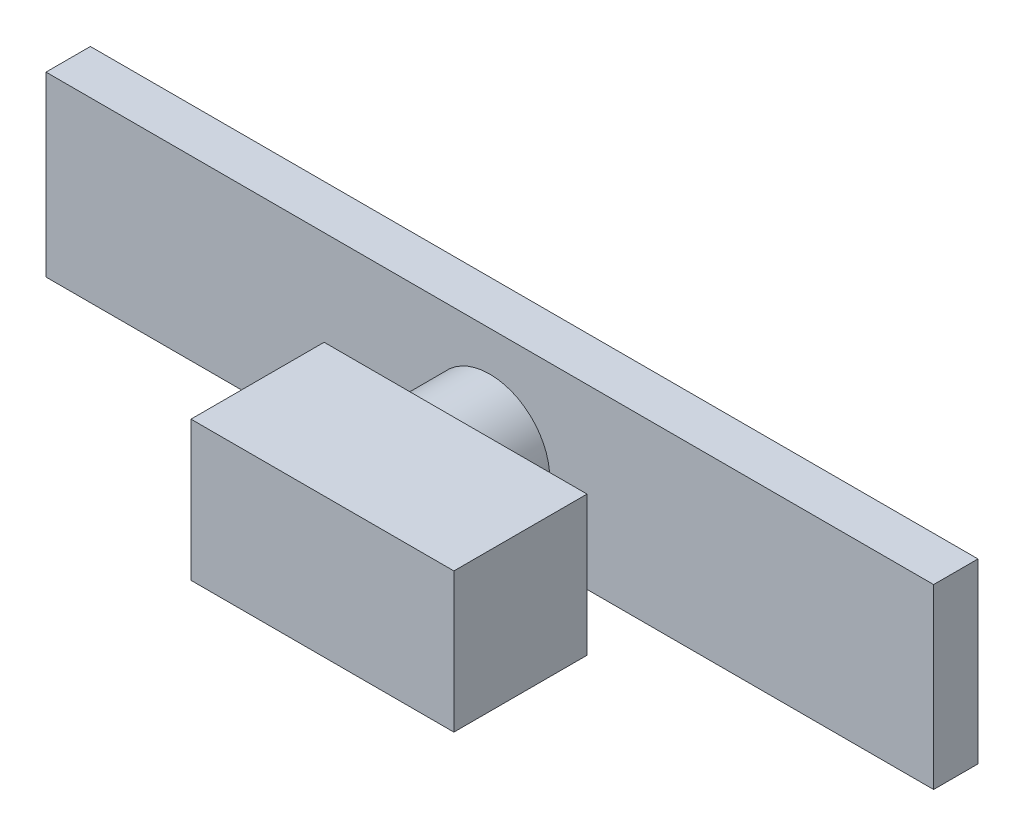
SolidWorks part; units mm, degrees
ref_plane "Front Plane" through (0, 0, 0) normal (0, 0, 1) x (1, 0, 0)
ref_plane "Top Plane" through (0, 0, 0) normal (0, 1, 0) x (1, 0, 0)
ref_plane "Right Plane" through (0, 0, 0) normal (1, 0, 0) x (0, 0, -1)
sketch "Sketch2" plane through (0, 0, 0) normal (0, 0, 1) x (1, 0, 0)
  line L1 (-47.8692, 21.2481) -> (206.1308, 21.2481)
  line L2 (-47.8692, 21.2481) -> (-47.8692, 8.5481)
  line L3 (-47.8692, 8.5481) -> (206.1308, 8.5481)
  line L4 (206.1308, 21.2481) -> (206.1308, 8.5481)
  dimension "D1" = 12.7
  dimension "D2" = 254
extrude "Boss-Extrude1" add sketch "Sketch2" along normal blind 50.8
sketch "Sketch3" plane through (0, 21.2481, 0) normal (0, 1, 0) x (1, 0, 0)
  circle A0 centre (79.1308, -28.4831) radius 17.1408
extrude "Boss-Extrude2" add sketch "Sketch3" along normal blind 19.05
sketch "Sketch4" plane through (0, 40.2981, 0) normal (0, 1, 0) x (1, 0, 0)
  line L1 (50.7675, -8.111) -> (126.0034, -8.111)
  line L2 (50.7675, -8.111) -> (50.7675, -48.0661)
  line L3 (50.7675, -48.0661) -> (126.0034, -48.0661)
  line L4 (126.0034, -8.111) -> (126.0034, -48.0661)
extrude "Boss-Extrude3" add sketch "Sketch4" along normal blind 38.1
scale "Scale2" scale about centroid uniform scaling yes scale factor 0.06
move or copy body "Body-Move/Copy1" bodies to move or copy 105 copy no rotation origin (0, 33.6669, 26.5501) rotation axis (1, 0, 0) rotation angle 90
move or copy body "Body-Move/Copy3" bodies to move or copy 106 copy no translate (-50.8, 0, -50.8)
scale "Scale5" scale about centroid uniform scaling yes scale factor 0.25
move or copy body "Body-Move/Copy9" bodies to move or copy 111 copy no translate (-50.8, 0, 0)
move or copy body "Body-Move/Copy11" bodies to move or copy 117 copy no translate (0, 0, -50.8)
move or copy body "Body-Move/Copy12" bodies to move or copy 119 copy no translate (0, 0, -127)
